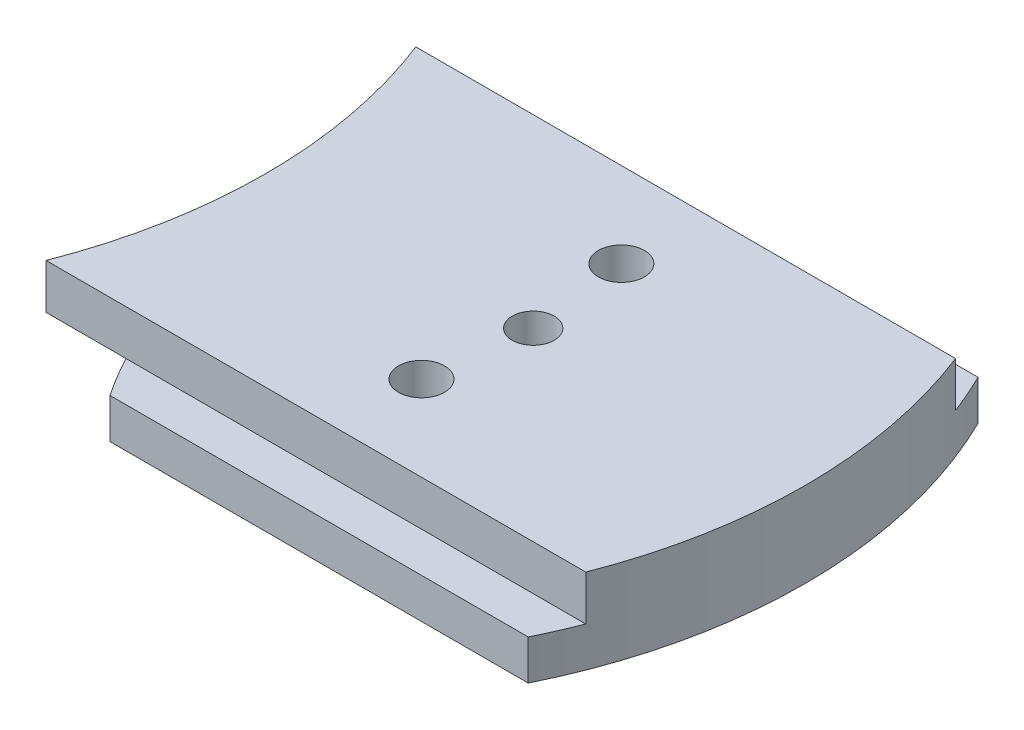
SolidWorks part; units mm, degrees
ref_plane "Спереди" through (0, 0, 0) normal (0, 0, 1) x (1, 0, 0)
ref_plane "Сверху" through (0, 0, 0) normal (0, 1, 0) x (1, 0, 0)
ref_plane "Справа" through (0, 0, 0) normal (1, 0, 0) x (0, 0, -1)
sketch "Эскиз1" plane through (0, 0, 0) normal (0, 1, 0) x (1, 0, 0)
  line L0 (0.8789, 20.5) -> (27.8789, 20.5)
  line L1 (0, 0) -> (27, 0)
  line L2 (0, 0) -> (0, 22.5) construction
  line L3 (0, 22.5) -> (27, 22.5)
  line L4 (27, 0) -> (27, 22.5) construction
  line L5 (0, 11.25) -> (27, 11.25) construction
  line L6 (0.8789, 2) -> (27.8789, 2)
  line L7 (0.8789, 20.5) -> (0.8789, 22.5)
  line L8 (0.8789, 2) -> (0.8789, 0)
  arc A0 (0, 22.5) -> (0, 0) centre (-22.8842, 11.25) cw
  arc A1 (27, 22.5) -> (27, 0) centre (4.1158, 11.25) cw
  circle A2 centre (16, 11.25) radius 1.05
  dimension "D1" = 22.5
  dimension "D2" = 25.5
  dimension "D4" = 2.1
  dimension "D3" = 2
  dimension "D5" = 16
  dimension "D6" = 11
extrude "Бобышка-Вытянуть1" add sketch "Эскиз1" along normal blind 2 contours A1 L3 A0 L0 | A1 L0 A0 L6 A2 | A1 L6 A0 L1 region at (14.1689, 0, -21.4945) region at (14.3789, 0, -20.1582) region at (14.1689, 0, -1.0055)
extrude "Бобышка-Вытянуть2" add sketch "Эскиз1<3>" along normal blind 2.25 from surface contours A1 L0 A0 L6 A2 region at (14.3789, 0, -20.1582) starting at face at (10.3114, 2, -11.25)
sketch "Эскиз1<3>" plane through (0, 0, 0) normal (0, 1, 0) x (1, 0, 0) same geometry as "Эскиз1"
sketch "Эскиз2" plane through (0, 0, 0) normal (0, -1, 0) x (1, 0, 0)
  line L0 (2.6158, -11.25) -> (29.6158, -11.25) construction
  line L11 (0.8789, 0) -> (27, 0) construction
  line L12 (0.8789, -22.5) -> (27, -22.5) construction
  line L13 (6.0798, 0) -> (0.8789, 0)
  line L14 (0.8789, 0) -> (0.8789, -22.5)
  line L15 (0.8789, -22.5) -> (6.0798, -22.5)
  arc A0 (0.8789, -20.5) -> (0.8789, -2) centre (-22.8842, -11.25) ccw construction
  arc A1 (27, -22.5) -> (27, 0) centre (4.1158, -11.25) ccw construction
  arc A2 (6.0798, 0) -> (6.0798, -22.5) centre (22.6158, -11.25) ccw
  dimension "D1" = 20
extrude "Вырез-Вытянуть1" cut sketch "Эскиз2" against normal up to surface (2 mm away) up to face at (14.1646, 2, -21.5024)
sketch "Эскиз3" plane through (0, 4.25, 0) normal (0, 1, 0) x (1, 0, 0)
  line L1 (27.8789, 2) -> (4.8834, 2) construction
  line L2 (27.8789, 2) -> (0.8789, 2) construction
  line L3 (27.8789, 20.5) -> (0.8789, 20.5) construction
  arc A0 (13.9084, 20.5) -> (13.9084, 2) centre (-5.5, 11.25) cw construction
  circle A1 centre (15.4105, 6.25) radius 1.15
  circle A2 centre (15.4105, 16.25) radius 1.15
  point P3 (16, 11.25)
  dimension "D1" = 21.5
  dimension "D2" = 10
  dimension "D3" = 2.3
extrude "Вырез-Вытянуть2" cut sketch "Эскиз3" against normal through all
chamfer "Фаска1" distance 1.2 angle 45 2 edges at (15.4105, 0, -15.1) (15.4105, 0, -5.1)
